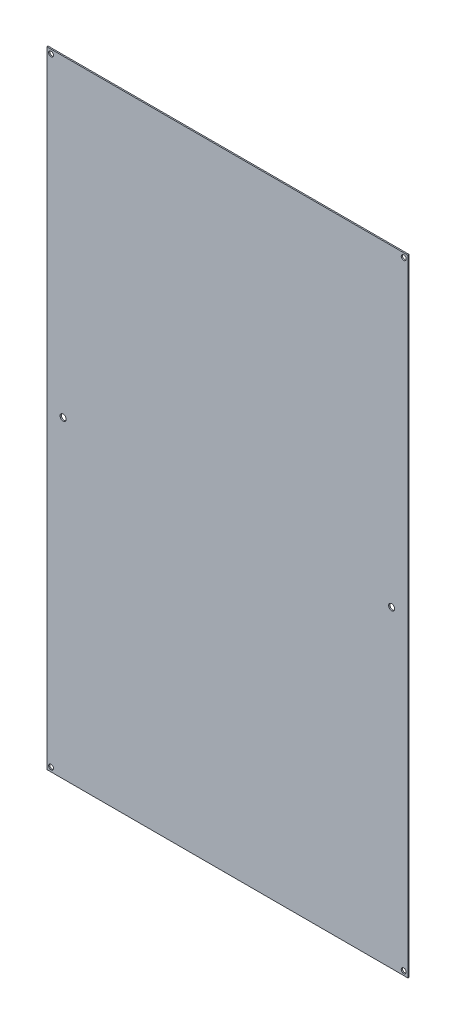
SolidWorks part; units mm, degrees
ref_plane "Front Plane" through (0, 0, 0) normal (0, 0, 1) x (1, 0, 0)
ref_plane "Top Plane" through (0, 0, 0) normal (0, 1, 0) x (1, 0, 0)
ref_plane "Right Plane" through (0, 0, 0) normal (1, 0, 0) x (0, 0, -1)
sketch "Sketch1" plane through (0, 0, 0) normal (0, 0, 1) x (1, 0, 0)
  line L1 (-109.8476, 958.0814) -> (-109.8476, 108.0814) construction
  line L2 (360.1524, 958.0814) -> (360.1524, 108.0814) construction
  line L3 (360.1524, 919.9815) -> (-109.8476, 919.9815) construction
  line L4 (-109.8476, 108.0814) -> (360.1524, 108.0814) construction
  line L5 (-109.8476, 919.9815) -> (-109.8476, 108.0814) construction
  line L6 (360.1524, 919.9815) -> (360.1524, 108.0814) construction
  line L7 (360.1524, 919.9815) -> (-109.8476, 919.9815) construction
  line L8 (-107.8476, 110.0814) -> (358.1524, 110.0814)
  line L9 (358.1524, 917.9815) -> (358.1524, 110.0814)
  line L10 (358.1524, 917.9815) -> (-107.8476, 917.9815)
  line L11 (-107.8476, 917.9815) -> (-107.8476, 110.0814)
  circle A0 centre (-102.4054, 115.5224) radius 3.175 construction
  circle A1 centre (352.7102, 115.5224) radius 3.175 construction
  circle A2 centre (-102.4054, 912.5404) radius 3.175 construction
  circle A3 centre (352.7102, 912.5404) radius 3.175 construction
  circle A4 centre (-102.4054, 115.5224) radius 3.175
  circle A5 centre (352.7102, 115.5224) radius 3.175
  circle A6 centre (-102.4054, 912.5404) radius 3.175
  circle A7 centre (352.7102, 912.5404) radius 3.175
  circle A8 centre (-86.8936, 514.0314) radius 3.9687 construction
  circle A9 centre (337.1984, 514.0314) radius 3.9688 construction
  circle A10 centre (-86.8936, 514.0314) radius 3.9687
  circle A11 centre (337.1984, 514.0314) radius 3.9688
  point P40 (232.1524, 398.9815)
  dimension "D1" = 126
  dimension "D2" = 519
  dimension "\"Panel_Offset\"" = 2
extrude "Boss-Extrude1" add sketch "Sketch1" along normal blind 1.6002
